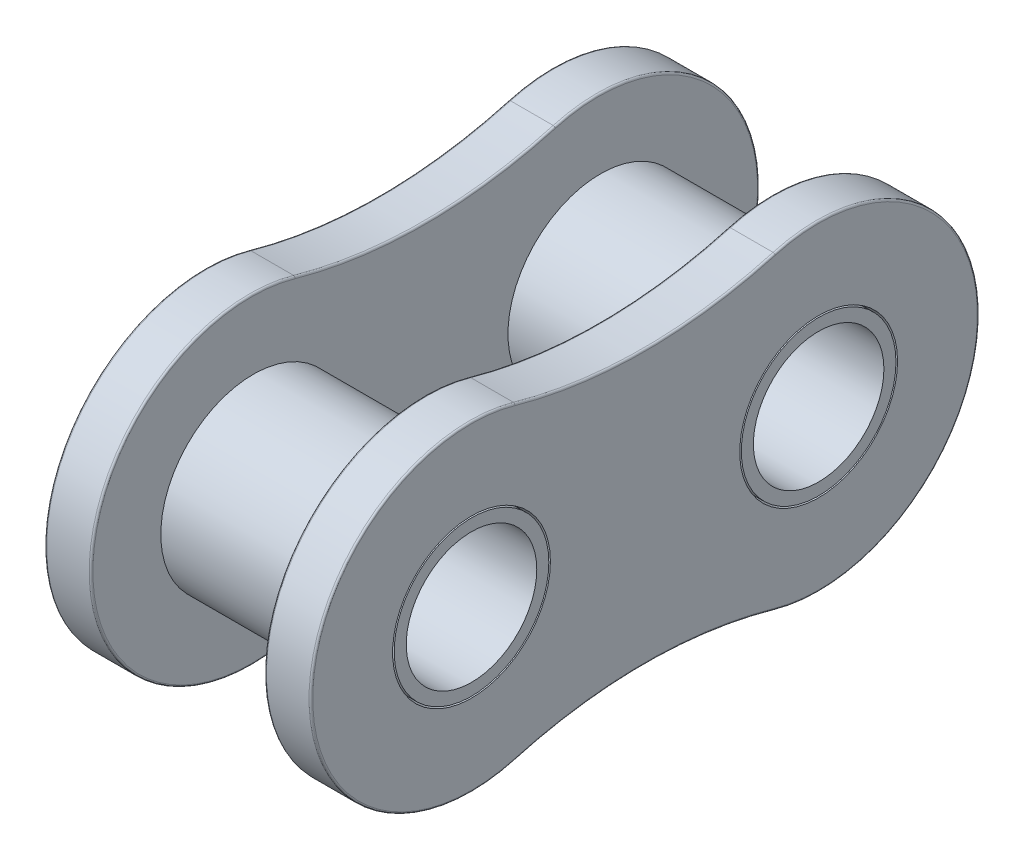
SolidWorks part; units mm, degrees
ref_plane "Front Plane" through (0, 0, 0) normal (0, 0, 1) x (1, 0, 0)
ref_plane "Top Plane" through (0, 0, 0) normal (0, 1, 0) x (1, 0, 0)
ref_plane "Right Plane" through (0, 0, 0) normal (1, 0, 0) x (0, 0, -1)
sketch "Sketch1" plane through (0, 0, 0) normal (1, 0, 0) x (0, 0, -1)
  line L0 (-4.7625, 0) -> (4.7625, 0) construction
  line L1 (-4.7625, 4.4069) -> (-4.7625, -4.4069) construction
  line L2 (4.7625, 4.4069) -> (4.7625, -4.4069) construction
  circle A0 centre (-4.7625, 0) radius 2.54 construction
  circle A1 centre (4.7625, 0) radius 2.54 construction
  circle A2 centre (-4.7625, 0) radius 1.7907 construction
  circle A3 centre (4.7625, 0) radius 1.7907 construction
  point P4 (0, 0)
  point P10 (-4.7625, 0)
  point P14 (4.7625, 0)
  dimension "Roller Diameter" = 5.08
  dimension "Pin Diameter" = 3.5814
  dimension "Plate Height" = 8.8138
  dimension "Pitch" = 9.525
sketch "Sketch2" plane through (0, 0, 0) normal (0, 1, 0) x (1, 0, 0)
  line L0 (-2.3812, 0) -> (2.3812, 0) construction
  point P0 (-3.6513, 0)
  point P3 (0, 0)
  point P4 (3.6513, 0)
  dimension "Roller Width" = 4.7625
  dimension "Plate Thickness" = 1.27
sketch "Sketch3" plane through (0, 0, 0) normal (1, 0, 0) x (0, 0, -1)
  line L0 (0, 3.7459) -> (0, -3.7459) construction
  line L1 (-4.7625, 1.7907) -> (-4.7625, 1.978) construction
  line L2 (-4.7625, 4.4069) -> (-4.7625, -4.4069) construction
  line L3 (-4.7625, 1.978) -> (-4.7625, 2.1654) construction
  line L4 (-4.7625, 2.1654) -> (-4.7625, 2.3527) construction
  line L5 (-4.7625, 2.3527) -> (-4.7625, 2.54) construction
  circle A2 centre (-4.7625, 0) radius 1.7907 construction
  circle A3 centre (-4.7625, 0) radius 2.54 construction
  arc A4 (-3.5623, 4.2403) -> (-3.5623, -4.2403) centre (-4.7625, 0) ccw
  arc A5 (3.5623, -4.2403) -> (3.5623, 4.2403) centre (4.7625, 0) ccw
  arc A6 (-3.5623, 4.2403) -> (3.5623, 4.2403) centre (0, 16.8255) ccw
  arc A7 (-3.5623, -4.2403) -> (3.5623, -4.2403) centre (0, -16.8255) cw
  circle A8 centre (-4.7625, 0) radius 2.1654
  circle A9 centre (4.7625, 0) radius 2.1654
  point P14 (0, 0)
  dimension "D2" = 4.3307
  dimension "D1" = 7.4917
extrude "Boss-Extrude1" add sketch "Sketch3" against normal up to vertex (-2.3813 mm away) from vertex up to point (2.3812, 0, 0) starting at point (3.6513, 0, 0)
fillet "Fillet1" radius 0.0508 8 edges at (2.3812, 3.7459, 0) (2.3812, 0, -9.1694) (2.3812, -3.7459, 0) (3.6513, 3.7459, 0) (3.6513, 0, -9.1694) (3.6513, -3.7459, 0) (2.3812, 0, 9.1694) (3.6513, 0, 9.1694)
mirror "Mirror1" about plane through (0, 0, 0) normal (1, 0, 0) of bodies 104
sketch "Sketch4" plane through (0, 0, 0) normal (1, 0, 0) x (0, 0, -1)
  circle A0 centre (-4.7625, 0) radius 2.54
  circle A1 centre (-4.7625, 0) radius 2.54 construction
  circle A2 centre (4.7625, 0) radius 2.54
  circle A3 centre (4.7625, 0) radius 2.54 construction
  circle A4 centre (-4.7625, 0) radius 1.7907
  circle A5 centre (4.7625, 0) radius 1.7907
  circle A6 centre (4.7625, 0) radius 1.7907 construction
  circle A7 centre (-4.7625, 0) radius 1.7907 construction
extrude "Boss-Extrude2" add sketch "Sketch4" along normal mid plane 4.6672 separate body
sketch "Sketch5" plane through (2.3336, 0, 0) normal (1, 0, 0) x (0, 0, -1)
  circle A1 centre (-4.7625, 0) radius 1.7907
  circle A2 centre (-4.7625, 0) radius 2.122
  circle A3 centre (-4.7625, 0) radius 2.122
  circle A4 centre (-4.7625, 0) radius 1.7907 construction
  dimension "D1" = 0.0433
extrude "Boss-Extrude3" add sketch "Sketch5" along normal up to surface (1.3176 mm away) separate body up to face at (3.6513, 0, 0)
sketch "Sketch6" plane through (2.3336, 0, 0) normal (1, 0, 0) x (0, 0, -1)
  circle A1 centre (4.7625, 0) radius 1.7907
  circle A2 centre (4.7625, 0) radius 2.1654 construction
  circle A3 centre (4.7625, 0) radius 2.122
  circle A4 centre (4.7625, 0) radius 1.7907 construction
  dimension "D1" = 0.0433
extrude "Boss-Extrude4" add sketch "Sketch6" along normal up to surface (1.3176 mm away) separate body up to face at (3.6513, 0, 0)
mirror "Mirror2" about plane through (0, 0, 0) normal (1, 0, 0) of bodies 108 109
sketch "Sketch7" plane through (0, 0, 0) normal (0, 1, 0) x (1, 0, 0)
  line L0 (-2.3812, -9.1694) -> (2.3812, -9.1694) construction
  line L2 (-2.3812, 0) -> (2.3812, 0) construction
  line L6 (2.3812, -9.1694) -> (3.6513, -9.1694) construction
  line L7 (-2.3812, -9.1694) -> (-3.6513, -9.1694) construction
  point P3 (0, -9.1694)
combine bodies "Combine1" operation type add bodies to combine 106 108 114
combine bodies "Combine2" operation type add bodies to combine 107 109 115
ref_plane "Plane1" through (0, 0, 0) normal (1, 0, 0) x (0, 0, -1)
equation "\"D1@Sketch2\"=\"Plate Thickness@Sketch2\""
equation "\"D1@Sketch3\"=\"Plate Height@Sketch1\"*.85"
equation "\"D1@Boss-Extrude2\"=\"Roller Width@Sketch2\"*.98"
equation "\"D1@Sketch6\"=\"D1@Sketch5\""
equation "\"D1@Sketch5\"=\"D2@Sketch3\"*.01"
equation "\"D1@Fillet1\"=\"Plate Thickness@Sketch2\"*.04"
